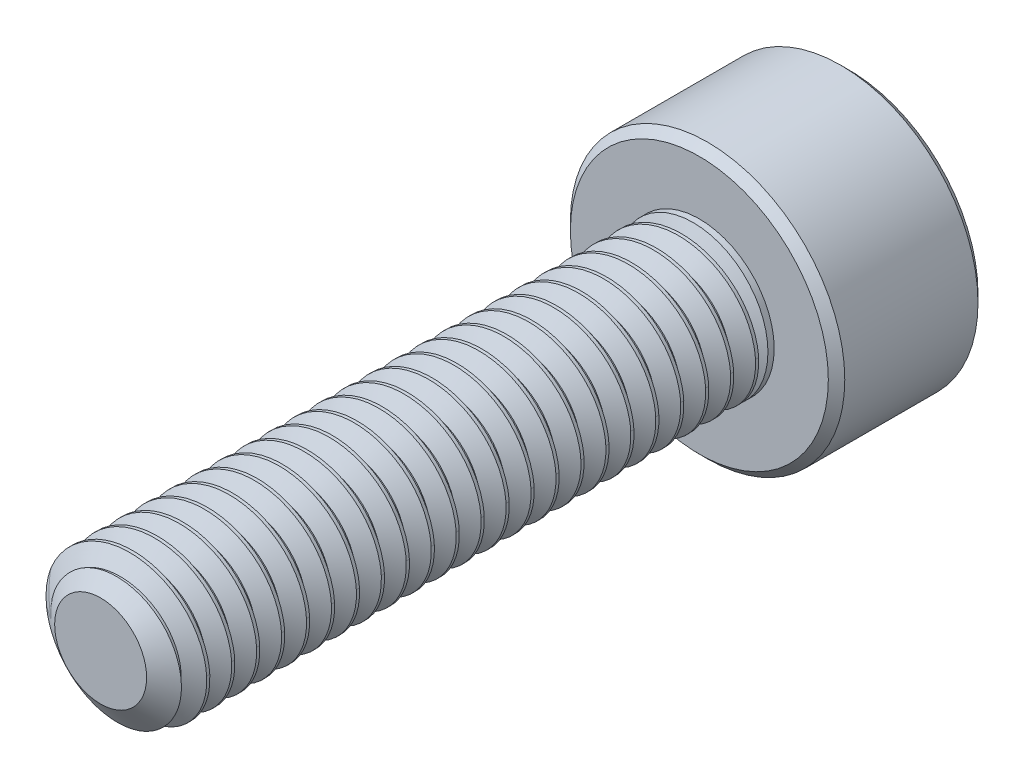
SolidWorks part; units mm, degrees
ref_plane "Front Plane" through (0, 0, 0) normal (0, 0, 1) x (1, 0, 0)
ref_plane "Top Plane" through (0, 0, 0) normal (0, 1, 0) x (1, 0, 0)
ref_plane "Right Plane" through (0, 0, 0) normal (1, 0, 0) x (0, 0, -1)
sketch "Sketch1" plane through (0, 0, 0) normal (0, 0, 1) x (1, 0, 0)
  circle A0 centre (0, 0) radius 1.5
  dimension "OD" = 3
extrude "Extrude1" add sketch "Sketch1" against normal blind 12
sketch "Sketch2" plane through (0, 0, 0) normal (0, 0, 1) x (1, 0, 0)
  circle A0 centre (0, 0) radius 1.5 construction
  circle A1 centre (0, 0) radius 1.5
curve "Helix/Spiral1" pitch 0.5 height 12.5 turns 25 parameters "pitch"=0.5
sketch "Sketch3" plane through (0, 0, 0) normal (1, 0, 0) x (0, 0, -1)
  line L0 (-0.4375, 1.5) -> (-0.25, 1.1752)
  line L1 (-0.25, 1.1752) -> (-0.1875, 1.1752)
  line L2 (-0.1875, 1.1752) -> (0, 1.5)
  line L3 (-0.4375, 1.5) -> (0, 1.5)
  line L4 (-0.2187, 1.5) -> (-0.2187, 1.1752) construction
  line L5 (-0.3437, 1.3376) -> (-0.0937, 1.3376) construction
  line L6 (0, 1.5) -> (0, -1.5) construction
  line L7 (0, -1.5) -> (12, -1.5) construction
  point P11 (2.25, -1.5)
  dimension "D1" = 0.0625
  dimension "D2" = 0.25
  dimension "D3" = 60
  dimension "D4" = 2.25
sweep "Cut-Sweep1" cut profiles "Sketch3" path "Helix/Spiral1"
sketch "Sketch4" plane through (0, 0, 0) normal (1, 0, 0) x (0, 0, -1)
  line L0 (0.4053, 1.5) -> (0, 0.9212)
  line L1 (0, 0.9212) -> (0, 1.5)
  line L2 (0.4053, 1.5) -> (0, 1.5)
  line L3 (-0.4375, 1.5) -> (0, 1.5) construction
  line L4 (0, 0) -> (7.0209, 0) construction
  dimension "D1" = 55
  dimension "D2" = 0.254
revolve "Cut-Revolve1" cut sketch "Sketch4" angle 360 about L4
sketch "Sketch5" plane through (0, 0, 0) normal (1, 0, 0) x (0, 0, -1)
  line L0 (12, -1.1822) -> (12, 1.0703) construction
  line L1 (12, 1.5) -> (0.1203, 1.5)
  line L2 (12, 1.5) -> (12, 0)
  line L3 (12, 0) -> (0.0001, 0)
  line L4 (0.0001, 1.1698) -> (0.0001, 0)
  line L5 (0.1203, 1.5) -> (0.0001, 1.1698)
  line L6 (0, 0) -> (9.9695, 0) construction
  point P3 (0.0001, 1.5)
  point P10 (0.0001, 1.5)
  dimension "D1" = 0.3302
  dimension "Thread min" = 0.0001
  dimension "D3" = 20
revolve "partially thread" [suppressed] add sketch "Sketch5" angle 360 about L6
sketch "Sketch6" plane through (0, 0, -12) normal (0, 0, -1) x (-1, 0, 0)
  circle A0 centre (0, 0) radius 2.75
  dimension "head dia" = 5.5
extrude "Extrude2" add sketch "Sketch6" along normal blind 3
sketch "Sketch7" plane through (0, 0, -15) normal (0, 0, -1) x (-1, 0, 0)
  line L1 (0, 1.4434) -> (-1.25, 0.7217)
  line L2 (-1.25, 0.7217) -> (-1.25, -0.7217)
  line L3 (-1.25, -0.7217) -> (0, -1.4434)
  line L4 (0, -1.4434) -> (1.25, -0.7217)
  line L5 (1.25, -0.7217) -> (1.25, 0.7217)
  line L6 (1.25, 0.7217) -> (0, 1.4434)
  circle A0 centre (0, 0) radius 1.25 construction
  dimension "hex dia" = 2.5
extrude "Cut-Extrude1" cut sketch "Sketch7" against normal blind 1.875
sketch "Sketch8" plane through (0, 0, -15) normal (0, 0, -1) x (-1, 0, 0)
  circle A0 centre (0, 0) radius 1.4434
extrude "Cut-Extrude2" cut sketch "Sketch8" against normal through all draft 45
chamfer "Chamfer1" distance 0.165 angle 45 2 edges at (-2.75, 0, -15) (-2.75, 0, -12)
sketch "Sketch9" plane through (0, 0, 0) normal (1, 0, 0) x (0, 0, -1)
  line L0 (0, 1.5) -> (0, -1.5) construction
  line L1 (2.75, 1.5) -> (2.75, -1.5) construction
  dimension "D1" = 2.75
sketch "Sketch10" plane through (0, 0, 0) normal (1, 0, 0) x (0, 0, -1)
  line L0 (12, 1.5) -> (12, 0)
  line L1 (12, 1.5) -> (11.875, 1.5)
  line L2 (11.875, 1.5) -> (11.2537, 0)
  line L3 (12, 0) -> (11.2537, 0)
  line L4 (12, 2.585) -> (12, -2.585) construction
  dimension "D1" = 22.5
  dimension "D2" = 0.125
revolve "Revolve1" add sketch "Sketch10" angle 360 about L3
equation "\"D3@Helix/Spiral1\" = \"screw length@Extrude1\"+\"pitch@Helix/Spiral1\""
equation "\"D1@Sketch3\" = \"pitch@Helix/Spiral1\"*.125"
equation "\"D2@Sketch3\" = \"pitch@Helix/Spiral1\"*.5"
equation "\"D1@Cut-Extrude1\" = \"hex dia@Sketch7\"*.75"
equation "\"D1@Chamfer1\" = \"head dia@Sketch6\"*.03"
equation "\"D1@Sketch9\" = \"pitch@Helix/Spiral1\"*5.5"
equation "\"D2@Sketch10\" = \"pitch@Helix/Spiral1\"*.25"
equation "\"D4@Sketch3\" = \"pitch@Helix/Spiral1\"*4.50"
